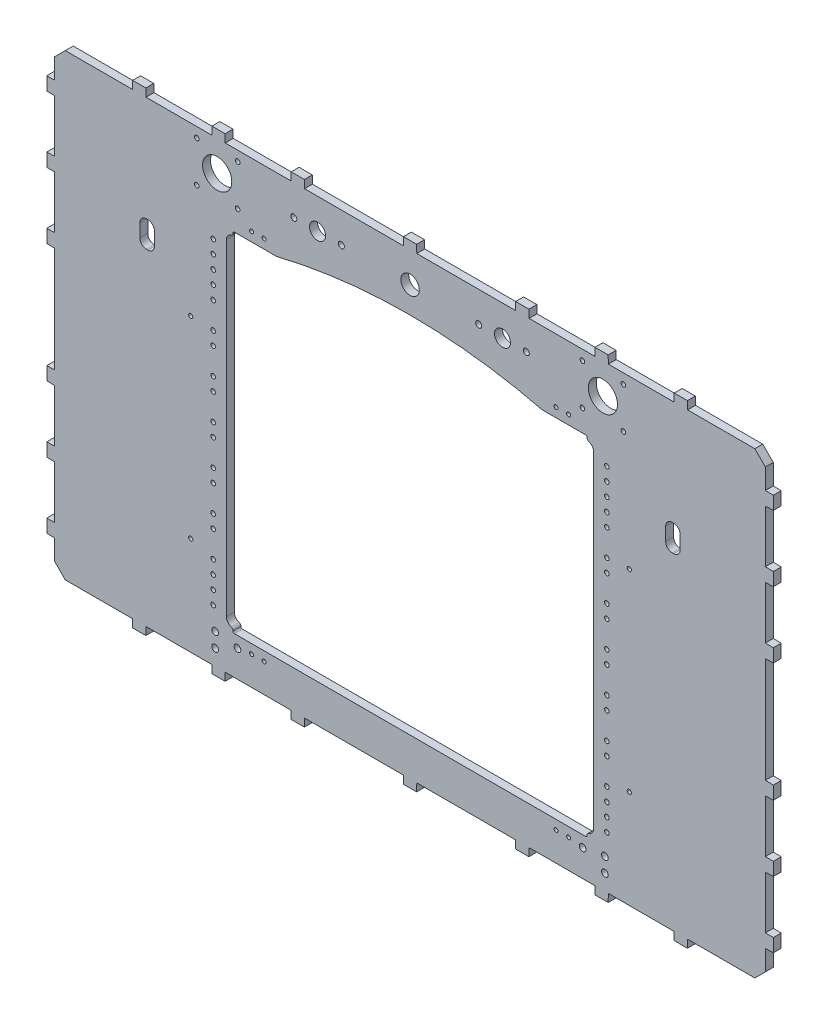
SolidWorks part; units mm, degrees
material "Клен"
ref_plane "Front" through (0, 0, 0) normal (0, 0, 1) x (1, 0, 0)
ref_plane "Top" through (0, 0, 0) normal (0, 1, 0) x (1, 0, 0)
ref_plane "Right" through (0, 0, 0) normal (1, 0, 0) x (0, 0, -1)
sketch "Эскиз1" plane through (0, 0, 0) normal (0, 0, 1) x (1, 0, 0)
  line L0 (2003.9536, 671.6913) -> (1788.4175, 671.6913) construction
  line L1 (1693.5805, 694.1913) -> (1693.5805, 791.8131) construction
  line L2 (1962.5805, 811.45) -> (1962.5805, 379.7662) construction
  line L3 (1554.5805, 451.4706) -> (1554.5805, 698.6913)
  line L4 (1559.5805, 705.6913) -> (1559.5805, 705.3995)
  line L5 (1560.5805, 706.6913) -> (1592.5638, 706.6913)
  line L6 (1862.5805, 811.45) -> (1862.5805, 379.7662) construction
  line L7 (1495.0805, 662.1297) -> (1494.0805, 662.1297)
  line L8 (1892.0805, 682.1297) -> (1893.0805, 682.1297)
  line L9 (1887.0805, 677.1297) -> (1887.0805, 667.1297)
  line L10 (1892.0805, 662.1297) -> (1893.0805, 662.1297)
  line L11 (1898.0805, 677.1297) -> (1898.0805, 667.1297)
  line L12 (1559.5805, 444.7624) -> (1559.5805, 444.4706)
  line L13 (1560.5805, 443.4706) -> (1826.5797, 443.4706)
  line L14 (1827.5797, 444.7624) -> (1827.5797, 444.4706)
  line L15 (1832.5805, 698.6913) -> (1832.5797, 451.4706)
  line L16 (1827.5805, 705.6913) -> (1827.5805, 705.3995)
  line L17 (1826.5805, 706.6913) -> (1793.6805, 706.6913)
  line L18 (1843.6805, 414.6913) -> (1893.4805, 414.6913)
  line L19 (1887.0805, 682.1297) -> (1898.0805, 662.1297) construction
  line L20 (1524.5805, 795.1278) -> (1524.5805, 392.3884) construction
  line L21 (1424.5805, 392.3884) -> (1424.5805, 795.1278) construction
  line L22 (1424.5805, 738.2913) -> (1418.5805, 738.1913)
  line L23 (1418.5805, 498.1913) -> (1418.5805, 488.1913)
  line L24 (1424.5805, 638.2913) -> (1418.5805, 638.1913)
  line L25 (1424.5805, 728.0913) -> (1424.5805, 688.2913)
  line L26 (1418.5805, 548.1913) -> (1418.5805, 538.1913)
  line L27 (1424.5805, 753.6913) -> (1424.5805, 738.2913)
  line L28 (1418.5805, 538.1913) -> (1424.5805, 538.0913)
  line L29 (1418.5805, 438.1913) -> (1424.5805, 438.0913)
  line L30 (1418.5805, 448.1913) -> (1418.5805, 438.1913)
  line L31 (1418.5805, 738.1913) -> (1418.5805, 728.1913)
  line L32 (1418.5805, 638.1913) -> (1418.5805, 628.1913)
  line L33 (1418.5805, 628.1913) -> (1424.5805, 628.0913)
  line L34 (1424.5805, 448.2913) -> (1418.5805, 448.1913)
  line L35 (1424.5805, 498.2913) -> (1418.5805, 498.1913)
  line L36 (1424.5805, 688.2913) -> (1418.5805, 688.1913)
  line L37 (1418.5805, 678.1913) -> (1424.5805, 678.0913)
  line L38 (1418.5805, 488.1913) -> (1424.5805, 488.0913)
  line L39 (1424.5805, 422.6913) -> (1432.5805, 414.6913)
  line L40 (1418.5805, 688.1913) -> (1418.5805, 678.1913)
  line L41 (1424.5805, 628.0913) -> (1424.5805, 548.2913)
  line L42 (1424.5805, 538.0913) -> (1424.5805, 498.2913)
  line L43 (1424.5805, 488.0913) -> (1424.5805, 448.2913)
  line L44 (1424.5805, 438.0913) -> (1424.5805, 422.6913)
  line L45 (1424.5805, 678.0913) -> (1424.5805, 638.2913)
  line L46 (1424.5805, 548.2913) -> (1418.5805, 548.1913)
  line L47 (1432.5805, 761.6913) -> (1424.5805, 753.6913)
  line L48 (1418.5805, 728.1913) -> (1424.5805, 728.0913)
  line L49 (1432.5805, 761.6913) -> (1483.4805, 761.6913)
  line L50 (1432.5805, 414.6913) -> (1483.4805, 414.6913)
  line L51 (1968.5805, 538.1913) -> (1968.5805, 548.1913)
  line L52 (1962.5805, 498.2913) -> (1962.5805, 538.0913)
  line L53 (1968.5805, 728.1913) -> (1968.5805, 738.1913)
  line L54 (1962.5805, 438.0913) -> (1968.5805, 438.1913)
  line L55 (1962.5805, 628.0913) -> (1968.5805, 628.1913)
  line L56 (1968.5805, 548.1913) -> (1962.5805, 548.2913)
  line L57 (1968.5805, 678.1913) -> (1968.5805, 688.1913)
  line L58 (1962.5805, 688.2913) -> (1962.5805, 728.0913)
  line L59 (1962.5805, 448.2913) -> (1962.5805, 488.0913)
  line L60 (1968.5805, 488.1913) -> (1968.5805, 498.1913)
  line L61 (1962.5805, 548.2913) -> (1962.5805, 628.0913)
  line L62 (1962.5805, 738.2913) -> (1962.5805, 753.6913)
  line L63 (1968.5805, 438.1913) -> (1968.5805, 448.1913)
  line L64 (1962.5805, 638.2913) -> (1962.5805, 678.0913)
  line L65 (1962.5805, 422.6913) -> (1962.5805, 438.0913)
  line L66 (1968.5805, 628.1913) -> (1968.5805, 638.1913)
  line L67 (1968.5805, 738.1913) -> (1962.5805, 738.2913)
  line L68 (1962.5805, 488.0913) -> (1968.5805, 488.1913)
  line L69 (1968.5805, 688.1913) -> (1962.5805, 688.2913)
  line L70 (1968.5805, 498.1913) -> (1962.5805, 498.2913)
  line L71 (1962.5805, 728.0913) -> (1968.5805, 728.1913)
  line L72 (1962.5805, 753.6913) -> (1954.5805, 761.6913)
  line L73 (1954.5805, 414.6913) -> (1962.5805, 422.6913)
  line L74 (1968.5805, 448.1913) -> (1962.5805, 448.2913)
  line L75 (1962.5805, 538.0913) -> (1968.5805, 538.1913)
  line L76 (1968.5805, 638.1913) -> (1962.5805, 638.2913)
  line L77 (1962.5805, 678.0913) -> (1968.5805, 678.1913)
  line L78 (1854.5805, 761.6913) -> (1893.4805, 761.6913)
  line L79 (1887.0805, 662.1297) -> (1898.0805, 682.1297) construction
  line L80 (1903.5805, 767.6913) -> (1893.5805, 767.6913)
  line L81 (1903.6805, 761.6913) -> (1903.5805, 767.6913)
  line L82 (1893.5805, 767.6913) -> (1893.4805, 761.6913)
  line L83 (1483.5805, 767.6913) -> (1483.4805, 761.6913)
  line L84 (1493.5805, 767.6913) -> (1483.5805, 767.6913)
  line L85 (1493.6805, 761.6913) -> (1493.5805, 767.6913)
  line L86 (1493.6805, 761.6913) -> (1532.5805, 761.6913)
  line L87 (1903.6805, 761.6913) -> (1954.5805, 761.6913)
  line L88 (1893.4805, 414.6913) -> (1893.5805, 408.6913)
  line L89 (1903.5805, 408.6913) -> (1903.6805, 414.6913)
  line L90 (1893.5805, 408.6913) -> (1903.5805, 408.6913)
  line L91 (1493.5805, 408.6913) -> (1493.6805, 414.6913)
  line L92 (1483.4805, 414.6913) -> (1483.5805, 408.6913)
  line L93 (1483.5805, 408.6913) -> (1493.5805, 408.6913)
  line L94 (1493.6805, 414.6913) -> (1532.5805, 414.6913)
  line L95 (1903.6805, 414.6913) -> (1954.5805, 414.6913)
  line L96 (1892.5805, 811.45) -> (1892.5805, 392.5098) construction
  line L97 (1494.5805, 795.1278) -> (1494.5805, 392.3884) construction
  line L98 (2003.9536, 706.6913) -> (1401.3159, 706.6913) construction
  line L99 (1489.0805, 677.1297) -> (1489.0805, 667.1297)
  line L104 (1495.0805, 682.1297) -> (1494.0805, 682.1297)
  line L105 (1500.0805, 677.1297) -> (1500.0805, 667.1297)
  line L106 (1859.5805, 811.45) -> (1859.5805, 401.8133) construction
  line L107 (1847.3817, 489.2413) -> (1981.6541, 489.2413) construction
  line L108 (1847.3817, 635.2413) -> (1981.6541, 635.2413) construction
  line L192 (1613.5805, 408.6913) -> (1613.6805, 414.6913)
  line L193 (1613.6805, 414.6913) -> (1688.4805, 414.6913)
  line L194 (1688.4805, 414.6913) -> (1688.5805, 408.6913)
  line L195 (1688.5805, 408.6913) -> (1698.5805, 408.6913)
  line L196 (1698.5805, 408.6913) -> (1698.6805, 414.6913)
  line L197 (1698.6805, 414.6913) -> (1773.4805, 414.6913)
  line L198 (1773.4805, 414.6913) -> (1773.5805, 408.6913)
  line L199 (1773.5805, 408.6913) -> (1783.5805, 408.6913)
  line L200 (1783.5805, 408.6913) -> (1783.6805, 414.6913)
  line L201 (1783.6805, 414.6913) -> (1833.4805, 414.6913)
  line L202 (1833.4805, 414.6913) -> (1833.5805, 408.6913)
  line L203 (1833.5805, 408.6913) -> (1843.5805, 408.6913)
  line L204 (1843.5805, 408.6913) -> (1843.6805, 414.6913)
  line L233 (1854.5805, 761.6913) -> (1843.6805, 761.6913)
  line L234 (1843.6805, 761.6913) -> (1843.5805, 767.6913)
  line L235 (1843.5805, 767.6913) -> (1833.5805, 767.6913)
  line L236 (1833.5805, 767.6913) -> (1833.4805, 761.6913)
  line L237 (1833.4805, 761.6913) -> (1783.6805, 761.6913)
  line L238 (1783.6805, 761.6913) -> (1783.5805, 767.6913)
  line L239 (1783.5805, 767.6913) -> (1773.5805, 767.6913)
  line L240 (1773.5805, 767.6913) -> (1773.4805, 761.6913)
  line L241 (1773.4805, 761.6913) -> (1698.6805, 761.6913)
  line L242 (1698.6805, 761.6913) -> (1698.5805, 767.6913)
  line L243 (1698.5805, 767.6913) -> (1688.5805, 767.6913)
  line L244 (1688.5805, 767.6913) -> (1688.4805, 761.6913)
  line L245 (1688.4805, 761.6913) -> (1613.6805, 761.6913)
  line L246 (1613.6805, 761.6913) -> (1613.5805, 767.6913)
  line L247 (1613.5805, 767.6913) -> (1603.5805, 767.6913)
  line L248 (1603.5805, 767.6913) -> (1603.4805, 761.6913)
  line L249 (1603.4805, 761.6913) -> (1553.6805, 761.6913)
  line L250 (1553.6805, 761.6913) -> (1553.5805, 767.6913)
  line L251 (1553.5805, 767.6913) -> (1543.5805, 767.6913)
  line L252 (1543.5805, 767.6913) -> (1543.4805, 761.6913)
  line L253 (1543.4805, 761.6913) -> (1532.5805, 761.6913)
  line L281 (1532.5805, 414.6913) -> (1543.4805, 414.6913)
  line L282 (1543.4805, 414.6913) -> (1543.5805, 408.6913)
  line L283 (1543.5805, 408.6913) -> (1553.5805, 408.6913)
  line L284 (1553.5805, 408.6913) -> (1553.6805, 414.6913)
  line L285 (1553.6805, 414.6913) -> (1603.4805, 414.6913)
  line L286 (1603.4805, 414.6913) -> (1603.5805, 408.6913)
  line L287 (1603.5805, 408.6913) -> (1613.5805, 408.6913)
  arc A0 (1893.0805, 662.1297) -> (1898.0805, 667.1297) centre (1893.0805, 667.1297) ccw
  arc A1 (1887.0805, 667.1297) -> (1892.0805, 662.1297) centre (1892.0805, 667.1297) ccw
  arc A2 (1893.0805, 682.1297) -> (1898.0805, 677.1297) centre (1893.0805, 677.1297) cw
  arc A3 (1892.0805, 682.1297) -> (1887.0805, 677.1297) centre (1892.0805, 677.1297) ccw
  arc A4 (1494.0805, 662.1297) -> (1489.0805, 667.1297) centre (1494.0805, 667.1297) cw
  arc A5 (1494.0805, 682.1297) -> (1489.0805, 677.1297) centre (1494.0805, 677.1297) ccw
  arc A6 (1500.0805, 667.1297) -> (1495.0805, 662.1297) centre (1495.0805, 667.1297) cw
  arc A7 (1495.0805, 682.1297) -> (1500.0805, 677.1297) centre (1495.0805, 677.1297) cw
  circle A8 centre (1859.5805, 489.2413) radius 1.6
  circle A9 centre (1859.5805, 635.2413) radius 1.6
  circle A10 centre (1527.5805, 489.2413) radius 1.6
  circle A11 centre (1527.5805, 635.2413) radius 1.6
  circle A69 centre (1804.0805, 436.4706) radius 1.5
  circle A70 centre (1813.5805, 436.4706) radius 1.5
  circle A71 centre (1824.2277, 434.9809) radius 2.55
  circle A72 centre (1841.0805, 426.6913) radius 2.55
  circle A73 centre (1841.0805, 437.6913) radius 2.55
  circle A74 centre (1842.5805, 454.1913) radius 1.75
  circle A75 centre (1842.5805, 464.1913) radius 1.75
  circle A76 centre (1842.5805, 474.1913) radius 1.75
  circle A77 centre (1842.5805, 484.1913) radius 1.75
  circle A78 centre (1842.5805, 504.1913) radius 1.75
  circle A79 centre (1842.5805, 514.1913) radius 1.75
  circle A80 centre (1842.5805, 534.1913) radius 1.75
  circle A81 centre (1842.5805, 544.1913) radius 1.75
  circle A82 centre (1842.5805, 564.1913) radius 1.75
  circle A83 centre (1842.5805, 574.1913) radius 1.75
  circle A84 centre (1842.5805, 594.1913) radius 1.75
  circle A85 centre (1842.5805, 604.1913) radius 1.75
  circle A86 centre (1842.5805, 624.1913) radius 1.75
  circle A87 centre (1842.5805, 634.1913) radius 1.75
  circle A88 centre (1842.5805, 654.1913) radius 1.75
  circle A89 centre (1842.5805, 664.1913) radius 1.75
  circle A90 centre (1842.5805, 674.1913) radius 1.75
  circle A91 centre (1842.5805, 684.1913) radius 1.75
  circle A92 centre (1842.5805, 694.1913) radius 1.75
  circle A93 centre (1583.0805, 436.4706) radius 1.5
  circle A94 centre (1573.5805, 436.4706) radius 1.5
  circle A95 centre (1562.9305, 434.9809) radius 2.55
  circle A96 centre (1546.0805, 426.6913) radius 2.55
  circle A97 centre (1546.0805, 437.6913) radius 2.55
  circle A98 centre (1544.5805, 454.1913) radius 1.75
  circle A99 centre (1544.5805, 464.1913) radius 1.75
  circle A100 centre (1544.5805, 474.1913) radius 1.75
  circle A101 centre (1544.5805, 484.1913) radius 1.75
  circle A102 centre (1544.5805, 504.1913) radius 1.75
  circle A103 centre (1544.5805, 514.1913) radius 1.75
  circle A104 centre (1544.5805, 534.1913) radius 1.75
  circle A105 centre (1544.5805, 544.1913) radius 1.75
  circle A106 centre (1544.5805, 564.1913) radius 1.75
  circle A107 centre (1544.5805, 574.1913) radius 1.75
  circle A108 centre (1544.5805, 594.1913) radius 1.75
  circle A109 centre (1544.5805, 604.1913) radius 1.75
  circle A110 centre (1544.5805, 624.1913) radius 1.75
  circle A111 centre (1544.5805, 634.1913) radius 1.75
  circle A112 centre (1544.5805, 654.1913) radius 1.75
  circle A113 centre (1544.5805, 664.1913) radius 1.75
  circle A114 centre (1544.5805, 674.1913) radius 1.75
  circle A115 centre (1544.5805, 684.1913) radius 1.75
  circle A116 centre (1544.5805, 694.1913) radius 1.75
  circle A117 centre (1804.0805, 713.6913) radius 1.5
  circle A118 centre (1813.5805, 713.6913) radius 1.5
  circle A119 centre (1824.0805, 723.1913) radius 1.75
  circle A120 centre (1855.0805, 723.1913) radius 1.75
  circle A121 centre (1839.5805, 738.6913) radius 11.05
  circle A122 centre (1855.0805, 754.1913) radius 1.75
  circle A123 centre (1824.0805, 754.1913) radius 1.75
  circle A124 centre (1781.5805, 738.6913) radius 2.3
  circle A125 centre (1763.5805, 738.6913) radius 6.05
  circle A126 centre (1745.5805, 738.6913) radius 2.3
  circle A127 centre (1693.5805, 738.6913) radius 7
  circle A128 centre (1641.5805, 738.6913) radius 2.3
  circle A129 centre (1623.5805, 738.6913) radius 6.05
  circle A130 centre (1605.5805, 738.6913) radius 2.3
  circle A131 centre (1583.0805, 713.6913) radius 1.5
  circle A132 centre (1573.5805, 713.6913) radius 1.5
  circle A133 centre (1563.0805, 723.1913) radius 1.75
  circle A134 centre (1563.0805, 754.1913) radius 1.75
  circle A135 centre (1547.5805, 738.6913) radius 11.05
  circle A136 centre (1532.0805, 723.1913) radius 1.75
  circle A137 centre (1532.0805, 754.1913) radius 1.75
  arc A142 (1793.6805, 706.6913) -> (1592.5638, 706.6913) centre (1693.1221, 296.6279) ccw
  arc A143 (1558.1519, 703.4829) -> (1554.5805, 698.6913) centre (1559.5805, 698.6913) ccw
  arc A144 (1558.1519, 703.4829) -> (1559.5805, 705.3995) centre (1557.5805, 705.3995) ccw
  arc A145 (1560.5805, 706.6913) -> (1559.5805, 705.6913) centre (1560.5805, 705.6913) ccw
  arc A155 (1559.5805, 444.4706) -> (1560.5805, 443.4706) centre (1560.5805, 444.4706) ccw
  arc A156 (1559.5805, 444.7624) -> (1558.1519, 446.6791) centre (1557.5805, 444.7624) ccw
  arc A157 (1554.5805, 451.4706) -> (1558.1519, 446.6791) centre (1559.5805, 451.4706) ccw
  arc A158 (1826.5797, 443.4706) -> (1827.5797, 444.4706) centre (1826.5797, 444.4706) ccw
  arc A159 (1829.0083, 446.6791) -> (1827.5797, 444.7624) centre (1829.5797, 444.7624) ccw
  arc A160 (1829.0083, 446.6791) -> (1832.5797, 451.4706) centre (1827.5797, 451.4706) ccw
  arc A161 (1832.5805, 698.6913) -> (1829.009, 703.4829) centre (1827.5805, 698.6913) ccw
  arc A162 (1827.5805, 705.3995) -> (1829.009, 703.4829) centre (1829.5805, 705.3995) ccw
  arc A163 (1827.5805, 705.6913) -> (1826.5805, 706.6913) centre (1826.5805, 705.6913) ccw
  point P48 (1892.5805, 672.1297)
  point P49 (1892.5805, 672.1297)
  dimension "D7" = 5
  dimension "D12" = 3.2
  dimension "D13" = 3.2
  dimension "D2" = 30
  dimension "D3" = 100
  dimension "D1" = 100
  dimension "D4" = 30
  dimension "D5" = 11
  dimension "D6" = 20
  dimension "D8" = 35
  dimension "D9" = 3
  dimension "D10" = 74.55
  dimension "D11" = 146
extrude "Бобышка-Вытянуть1" add sketch "Эскиз1" along normal blind 6
